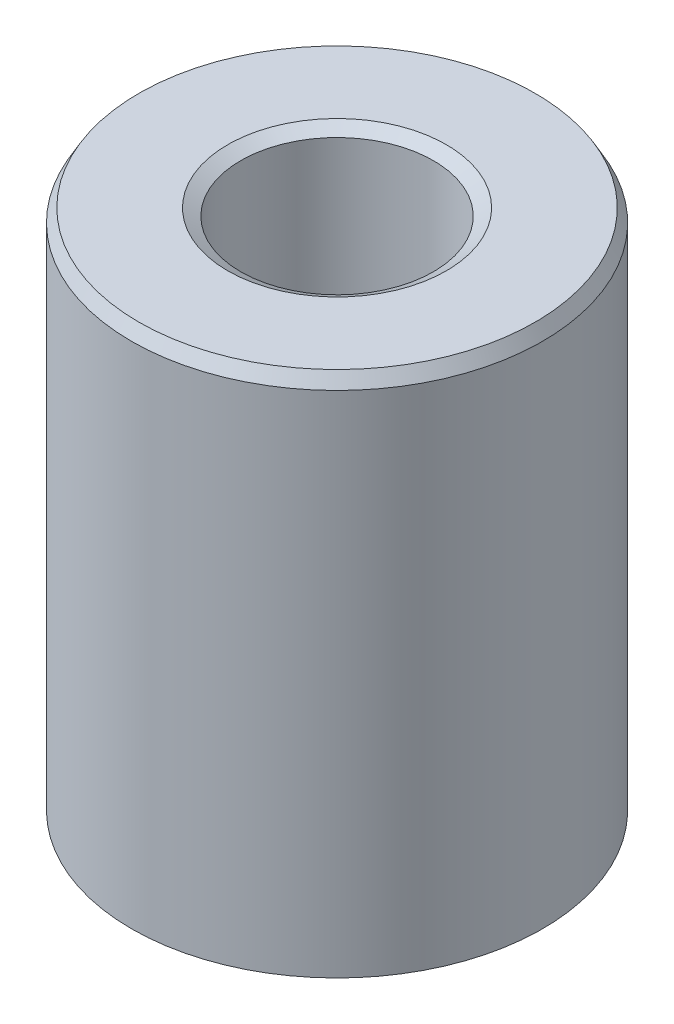
SolidWorks part; units mm, degrees
ref_plane "Front Plane" through (0, 0, 0) normal (0, 0, 1) x (1, 0, 0)
ref_plane "Top Plane" through (0, 0, 0) normal (0, 1, 0) x (1, 0, 0)
ref_plane "Right Plane" through (0, 0, 0) normal (1, 0, 0) x (0, 0, -1)
sketch "Sketch1" plane through (0, 0, 0) normal (0, 1, 0) x (1, 0, 0)
  circle A0 centre (0, 0) radius 10
  dimension "SLEEVE_OD" = 20
extrude "Boss-Extrude1" add sketch "Sketch1" along normal blind 25.7474
sketch "Sketch2" plane through (0, 0, 0) normal (0, 1, 0) x (1, 0, 0)
  circle A0 centre (0, 0) radius 4.6887
  dimension "BORE_D" = 9.3774
extrude "Cut-Extrude1" cut sketch "Sketch2" along normal through all
chamfer "Chamfer1" distance 0.631 angle 29.417 4 edges at (0, 25.7474, 4.6887) (0, 0, 4.6887) (0, 0, 10) (0, 25.7474, 10) first distance on face at (0, 25.7474, 4.6887) first distance on face at (0, 0, 4.6887) first distance on face at (0, 25.7474, 10)
